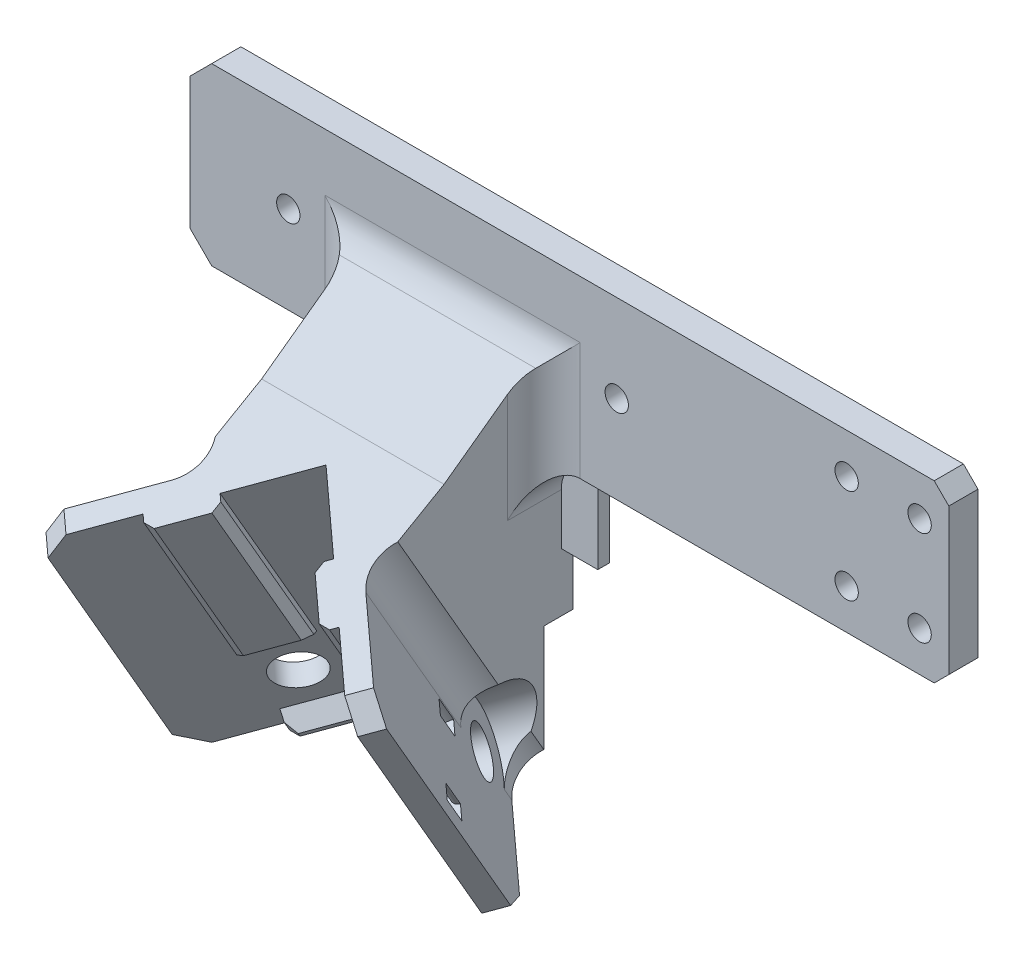
SolidWorks part; units mm, degrees
ref_plane "Alzado" through (0, 0, 0) normal (0, 0, 1) x (1, 0, 0)
ref_plane "Planta" through (0, 0, 0) normal (0, 1, 0) x (1, 0, 0)
ref_plane "Vista lateral" through (0, 0, 0) normal (1, 0, 0) x (0, 0, -1)
sketch "Croquis1" plane through (0, 0, 0) normal (0, 0, 1) x (1, 0, 0)
  line L0 (0, 0) -> (0, 18835.1574) construction
  line L1 (0, 0) -> (-18835.1574, 0) construction
  line L2 (12.5, -12) -> (36, -12)
  line L3 (-36, -12) -> (36, -12) construction
  line L4 (-36, -12) -> (-36, 12)
  line L5 (-36, 12) -> (36, 12)
  line L6 (36, -12) -> (36, 12)
  line L7 (-36, -12) -> (36, 12) construction
  line L8 (-36, 12) -> (36, -12) construction
  line L9 (-17.5, 6) -> (17.5, 6) construction
  line L10 (-17.5, 6) -> (-17.5, -6) construction
  line L11 (-17.5, -6) -> (17.5, -6) construction
  line L12 (17.5, 6) -> (17.5, -6) construction
  line L13 (-17.5, 6) -> (17.5, -6) construction
  line L14 (-17.5, -6) -> (17.5, 6) construction
  line L15 (-12.5, -32) -> (12.5, -32)
  line L16 (-12.5, -32) -> (-12.5, -12)
  line L17 (-12.5, -12) -> (12.5, -12) construction
  line L18 (12.5, -32) -> (12.5, -12)
  line L19 (-12.5, -32) -> (12.5, -12) construction
  line L20 (-12.5, -12) -> (12.5, -32) construction
  line L21 (-36, -12) -> (-12.5, -12)
  circle A0 centre (-22.5, 0) radius 1.6
  circle A1 centre (22.5, 0) radius 1.6
  point P7 (0, 0)
  point P12 (0, -22)
  point P16 (0, 0)
  dimension "D1" = 3.2
  dimension "D2" = 45
  dimension "D3" = 24
  dimension "D4" = 13.5
  dimension "D5" = 35
  dimension "D6" = 12
  dimension "D7" = 20
  dimension "D8" = 25
extrude "Saliente-Extruir1" add sketch "Croquis1" along normal blind 4
sketch "Croquis3" plane through (0, 0, 0) normal (0, 0, -1) x (-1, 0, 0)
  line L0 (0, 0) -> (-50000, 0) construction
  line L1 (-66, 12) -> (-36, 12)
  line L2 (-66, -12) -> (-36, -12)
  line L3 (-36, -12) -> (-36, 12)
  line L4 (-36, -12) -> (-36, 12) construction
  line L5 (-66, 12) -> (-68, 10)
  line L6 (-68, 10) -> (-68, -10)
  line L7 (-66, -12) -> (-68, -10)
  arc A0 (-66, 12) -> (-66, -12) centre (-66, 0) ccw construction
  circle A1 centre (-54, 6.5) radius 1.6
  circle A2 centre (-64, 6.5) radius 1.6
  circle A3 centre (-54, -6.5) radius 1.6
  circle A4 centre (-64, -6.5) radius 1.6
  point P22 (-68, 0)
  dimension "D1" = 30
  dimension "D2" = 3.2
  dimension "D5" = 28
  dimension "D3" = 13
  dimension "D4" = 18
  dimension "D6" = 32
  dimension "D7" = 2
extrude "Saliente-Extruir3" add sketch "Croquis3" against normal blind 4
ref_plane "Plano1" through (0, -7.2679, -4.1962) normal (0, -0.866, -0.5) x (1, 0, 0)
sketch "Croquis5" plane through (0, -7.4101, -3.95) normal (0, 0.866, 0.5) x (1, 0, 0)
  line L0 (0, 0) -> (0, 50000) construction
  line L2 (-21.2132, -44.6357) -> (0, -23.4225) construction
  line L5 (-13.435, -36.8575) -> (-21.2132, -44.6357)
  line L11 (-10, -9.1798) -> (49990, -9.1798) construction
  line L12 (0, -19.1798) -> (23.3345, -42.5144)
  line L13 (23.3345, -42.5144) -> (21.2132, -44.6357)
  line L14 (21.2132, -44.6357) -> (0, -23.4225) construction
  line L38 (11.9344, -32.7013) -> (35367.2734, 35322.6378) construction
  line L39 (0, -23.4225) -> (-7.7782, -31.2006)
  line L40 (7.7782, -31.2006) -> (6.364, -32.6149)
  line L41 (6.364, -32.6149) -> (12.0208, -38.2717)
  line L42 (12.0208, -38.2717) -> (13.435, -36.8575)
  line L43 (0, -23.4225) -> (7.7782, -31.2006)
  line L44 (13.435, -36.8575) -> (21.2132, -44.6357)
  line L45 (-12.0208, -38.2717) -> (-13.435, -36.8575)
  line L46 (-6.364, -32.6149) -> (-12.0208, -38.2717)
  line L47 (-7.7782, -31.2006) -> (-6.364, -32.6149)
  line L48 (-23.3345, -42.5144) -> (-21.2132, -44.6357)
  line L49 (0, -19.1798) -> (-23.3345, -42.5144)
  point P13 (10.6066, -34.0291)
  point P19 (9.1924, -35.4433)
  dimension "D1" = 45
  dimension "D2" = 30
  dimension "D3" = 3
  dimension "D4" = 2
  dimension "D5" = 8
  dimension "D6" = 10
extrude "Saliente-Extruir4" add sketch "Croquis5" against normal blind 30 and the other way blind 10
sketch "Croquis13" plane through (-13.2676, -6.6338, 11.4901) normal (-0.7071, -0.3536, 0.6124) x (0.5078, 0.3488, 0.7877)
  line L0 (-1.9628, -47.6691) -> (22715.9707, 23396.5113) construction
  line L1 (-6.7791, -46.8914) -> (-1.034, -52.4586) construction
  line L3 (21.0567, -18.1657) -> (26.8019, -23.7329) construction
  circle A0 centre (1.6606, -43.9299) radius 3.1
  point P4 (-3.9066, -49.675)
  point P9 (23.9293, -20.9493)
  dimension "D1" = 6.2
  dimension "D2" = 8
extrude "Cortar-Extruir8" cut sketch "Croquis13" against normal up to next (5 mm away)
sketch "Croquis14" plane through (-13.2676, -6.6338, 11.4901) normal (-0.7071, -0.3536, 0.6124) x (0.5078, 0.3488, 0.7877)
  line L0 (-4.3435, -44.3779) -> (1.4017, -49.9451)
  line L1 (21.0567, -18.1657) -> (-6.7791, -46.8914) construction
  line L2 (26.8019, -23.7329) -> (-1.034, -52.4586) construction
  line L3 (1.4017, -49.9451) -> (7.6647, -43.4818)
  line L4 (26.8019, -23.7329) -> (-1.034, -52.4586) construction
  line L5 (7.6647, -43.4818) -> (1.9196, -37.9147)
  line L6 (21.0567, -18.1657) -> (-6.7791, -46.8914) construction
  line L7 (1.9196, -37.9147) -> (-4.3435, -44.3779)
  line L8 (-1.212, -41.1463) -> (4.5332, -46.7135) construction
  point P16 (1.6606, -43.9299)
  dimension "D1" = 9
extrude "Cortar-Extruir9" cut sketch "Croquis14" against normal up to surface (2 mm away) up to face at (17.3241, -36.4436, 26.3376)
sketch "Croquis15" plane through (9.4562, -4.0161, 17.4023) normal (0.7071, -0.3536, 0.6124) x (0.6987, 0.2164, -0.6819)
  line L0 (-8.4296, -38.5546) -> (45221.4788, 2522.3506) construction
  line L2 (-25.0764, -10.3807) -> (7521.825, -48568.2342) construction
  line L3 (-29.4576, -8.2371) -> (-21.5525, -7.0085) construction
  line L4 (-23.3145, -47.7626) -> (-15.4094, -46.534) construction
  circle A0 centre (-20.5906, -39.2432) radius 3.1
  point P8 (-25.505, -7.6228)
  point P11 (-19.3619, -47.1483)
  dimension "D1" = 6.2
  dimension "D2" = 8
extrude "Cortar-Extruir10" cut sketch "Croquis15" against normal up to next (5 mm away)
sketch "Croquis17" plane through (9.4562, -4.0161, 17.4023) normal (0.7071, -0.3536, 0.6124) x (0.6987, 0.2164, -0.6819)
  line L0 (-23.852, -44.3041) -> (-15.9469, -43.0755)
  line L3 (-15.9469, -43.0755) -> (-17.3291, -34.1823)
  line L5 (-17.3291, -34.1823) -> (-25.2342, -35.4109)
  line L7 (-25.2342, -35.4109) -> (-23.852, -44.3041)
  line L8 (-24.5431, -39.8575) -> (-16.638, -38.6289) construction
  line L10 (-21.5525, -7.0085) -> (-15.4094, -46.534) construction
  line L11 (-29.4576, -8.2371) -> (-23.3145, -47.7626) construction
  line L12 (-29.4576, -8.2371) -> (-23.3145, -47.7626) construction
  point P2 (-13.1428, -24.272)
  point P3 (-20.5906, -39.2432)
  point P11 (-20.5906, -39.2432)
  point P16 (-12.3183, -37.9575)
  dimension "D1" = 9
extrude "Cortar-Extruir11" cut sketch "Croquis17" against normal up to surface (2 mm away) up to face at (-17.3241, -36.4436, 26.3376)
sketch "Croquis19" plane through (0, 0, 0) normal (1, 0, 0) x (0, 0, -1)
  line L0 (-17.6603, -8.3397) -> (-24, -12)
  line L1 (-17.8685, -54.648) -> (2.3397, -42.9808) construction
  line L2 (-24, -12) -> (-4, -46.641)
  line L3 (-4, -32) -> (-4, -12) construction
  line L4 (-4, -46.641) -> (-4, 1.6)
  line L6 (-4, 1.6) -> (-17.6603, -8.3397)
  line L9 (-17.6603, -8.3397) -> (-37.8685, -20.007) construction
  point P3 (-4, -46.641)
extrude "Saliente-Extruir5" add sketch "Croquis19" along normal mid plane 25
sketch "Croquis18" plane through (0, 1.3923, 0.8038) normal (0, 0.866, 0.5) x (1, 0, 0)
  line L1 (12.5, -26.7846) -> (7.3205, -26.7846) construction
  line L2 (3.0779, -26.7846) -> (7.7782, -31.4849) construction
  line L5 (-7.7782, -31.4849) -> (-3.0779, -26.7846) construction
  line L7 (0, -23.7067) -> (3.0779, -26.7846)
  line L10 (3.0779, -26.7846) -> (-3.0779, -26.7846)
  line L11 (0, -23.7067) -> (-3.0779, -26.7846)
  point P1 (3.0779, -26.7846)
  point P6 (-3.0779, -26.7846)
extrude "Cortar-Extruir12" cut sketch "Croquis18" against normal through all
fillet "Redondeo1" radius 5 7 edges at (-12.5, -5.2, 4) (12.5, -5.2, 4) (7.3205, -29.3205, 14) (-7.3205, -29.3205, 14) (-12.5, -12, 2) (12.5, -12, 2) (0, 1.6, 4)
chamfer "Chaflán1" distance 3 angle 45 10 edges at (22.2739, -55.1784, 18.7871) (22.2739, -20.5373, 38.7871) (-22.2739, -55.1784, 18.7871) (-22.2739, -20.5373, 38.7871) (-36, -12, 2) (-36, 12, 2) (9.1924, -40.2872, 17.9948) (-9.1924, -40.2872, 17.9948) (-9.1924, -48.0814, 13.4948) (9.1924, -48.0814, 13.4948)
fillet "Redondeo2" [suppressed] radius 5
sketch "Croquis20" plane through (0, 0, 0) normal (0, 0, -1) x (-1, 0, 0)
  line L0 (0, 0) -> (0, 50000) construction
  line L1 (-17.5, -12) -> (49982.5, -12) construction
  line L2 (-42.5097, -24) -> (49957.4903, -24) construction
  line L4 (-17.5, -24) -> (17.5, -24)
  line L5 (-17.5, -24) -> (-17.5, -12)
  line L6 (-17.5, -12) -> (17.5, -12)
  line L7 (17.5, -24) -> (17.5, -12)
  line L8 (-17.5, -24) -> (17.5, -12) construction
  line L9 (-17.5, -12) -> (17.5, -24) construction
  point P8 (0, -18)
  dimension "D1" = 12
extrude "Saliente-Extruir6" add sketch "Croquis20" against normal blind 1.6
sketch "Croquis23" plane through (0, -33.2487, -19.1962) normal (0, -0.866, -0.5) x (1, 0, 0)
  line L0 (21.2132, 40.6773) -> (13.3169, 32.781) construction
  line L1 (14.92, 35.7983) -> (19.0919, 39.9702)
  line L2 (23.3345, 42.7986) -> (21.2132, 40.6773) construction
  line L3 (17.6777, 41.3844) -> (13.5057, 37.2125)
  line L4 (13.5057, 32.9698) -> (14.92, 34.3841)
  line L5 (20.5061, 39.9702) -> (21.9203, 41.3844)
  line L6 (13.435, 37.1418) -> (19.0919, 42.7986) construction
  line L7 (21.2132, 44.9199) -> (23.3345, 42.7986) construction
  arc A0 (14.92, 34.3841) -> (14.92, 35.7983) centre (15.6271, 35.0912) cw
  arc A1 (19.0919, 39.9702) -> (20.5061, 39.9702) centre (19.799, 39.2631) cw
  arc A2 (21.9203, 41.3844) -> (17.6777, 41.3844) centre (19.799, 39.2631) ccw
  arc A3 (13.5057, 37.2125) -> (13.5057, 32.9698) centre (15.6271, 35.0912) ccw
  dimension "D1" = 2
  dimension "D3" = 2
  dimension "D2" = 2
extrude "Cortar-Extruir13" cut sketch "Croquis23" against normal blind 4 from offset 16 offset against normal yes
sketch "Croquis25" plane through (0, 0, 0) normal (0, 0, -1) x (-1, 0, 0)
  line L0 (5.9326, -30.1966) -> (11.0955, -30.1966) construction
  text T0 "30"
  point P3 (11.0955, -29.4665)
  point P4 (5.9326, -30.1966)
extrude "Cortar-Extruir14" cut sketch "Croquis25" against normal blind 1
chamfer "Chaflán2" distance 1 angle 45 7 edges at (-6.364, -49.4818, 9.4203) (-12.0208, -52.3102, 14.3193) (12.0208, -52.3102, 14.3193) (-12.0208, -28.4945, 28.0693) (-6.364, -25.6661, 23.1703) (12.0208, -28.4945, 28.0693) (6.364, -25.6661, 23.1703)
sketch "Croquis26" plane through (-9.7321, -4.866, 8.4282) normal (0.7071, 0.3536, -0.6124) x (-0.5477, -0.2739, -0.7906)
  circle A0 centre (-5.3819, -43.6306) radius 6
  dimension "D1" = 12
extrude "Cortar-Extruir15" cut sketch "Croquis26" along normal through all
sketch "Croquis27" plane through (9.7321, -4.866, 8.4282) normal (-0.7071, 0.3536, -0.6124) x (-0.5477, 0.2739, 0.7906)
  circle A0 centre (5.3819, -43.6306) radius 6
  dimension "D1" = 12
extrude "Cortar-Extruir16" cut sketch "Croquis27" along normal through all
